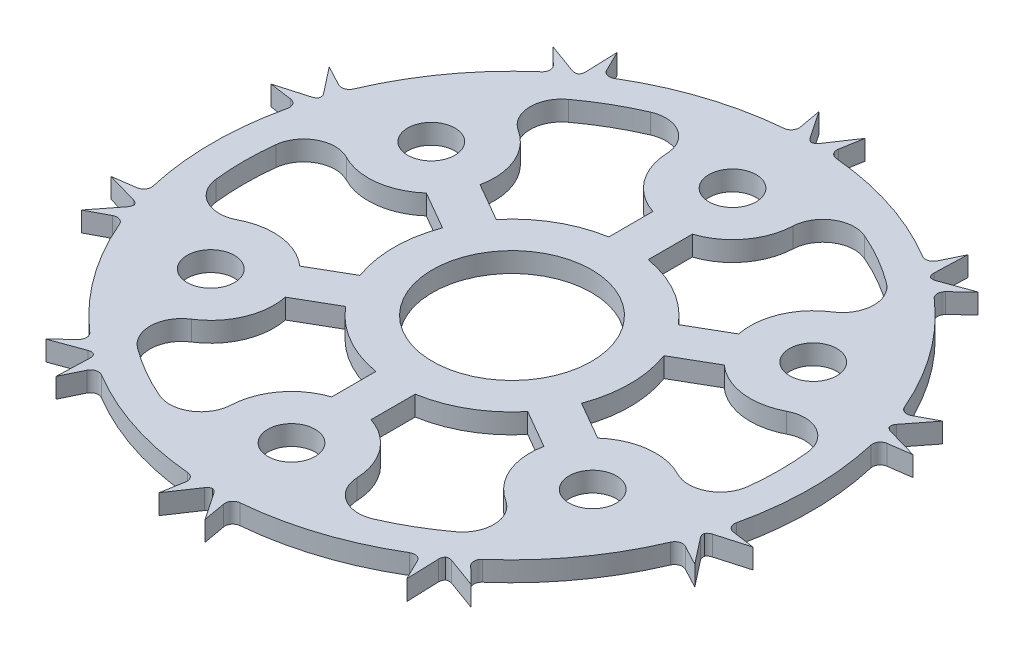
SolidWorks part; units mm, degrees
note: '?' marks a value the reader was unsure of.
material "Commercially Pure CP-Ti UNS R50700  Grade 4 (SS)"
ref_plane "Front Plane" through (0, 0, 0) normal (0, 0, 1) x (1, 0, 0)
ref_plane "Top Plane" through (0, 0, 0) normal (0, 1, 0) x (1, 0, 0)
ref_plane "Right Plane" through (0, 0, 0) normal (1, 0, 0) x (0, 0, -1)
other "Bounding Box"
ref_plane "Default Plane" through (13.8565, 3.175, 6.7999) normal (0, -1, 0) x (-1, 0, 0)
sketch "Sketch1" plane through (0, 0, 0) normal (0, 1, 0) x (1, 0, 0)
  line L0 (17.9605, -17.9605) -> (0, 0) construction
  line L1 (0, 0) -> (17.9605, 17.9605) construction
  line L2 (0, 0) -> (0, 25.4) construction
  circle A0 centre (0, 0) radius 25.4
  point P3 (0, 25.4)
  point P4 (25.4, 0)
  point P5 (-25.4, 0)
  point P6 (0, -25.4)
  point P7 (17.9605, 17.9605)
  point P8 (17.9605, -17.9605)
  dimension "D1" = 50.8
  dimension "D2" = 45
extrude "Boss-Extrude1" add sketch "Sketch1" along normal mid plane 15.24
ref_plane "Plane2" through (-25.4, 0, 0) normal (-1, 0, 0) x (0, 0, 1)
sketch "Sketch9" plane through (-25.4, 0, 0) normal (-1, 0, 0) x (0, 0, 1)
  line L0 (-0.635, -7.62) -> (0.635, -7.62)
  line L1 (-25.4, -7.62) -> (25.4, -7.62) construction
  line L2 (0.635, -7.62) -> (0.635, 0)
  line L3 (25.4, 7.62) -> (-25.4, 7.62) construction
  line L5 (-0.635, 0) -> (-0.635, -7.62)
  line L6 (0.635, -7.62) -> (0, -7.62) construction
  line L7 (0, -7.62) -> (0, 7.62) construction
  line L9 (-0.635, 0) -> (0.635, 0) construction
  line L10 (0.635, 0) -> (0.635, 7.62)
  line L11 (0.635, 7.62) -> (-0.635, 7.62)
  line L13 (-0.635, 7.62) -> (-0.635, 0)
  point P14 (0, 0)
  dimension "D2" = 1.27
extrude "Cut-Extrude4" cut sketch "Sketch9" against normal blind 0.635
sketch "Sketch4" plane through (0, 0, 0) normal (0, 0, 1) x (1, 0, 0)
  line L0 (-25.4, -7.62) -> (-22.225, -7.62)
  line L1 (-25.3921, -7.62) -> (25.4, -7.62) construction
  line L4 (25.4, 7.62) -> (-25.3921, 7.62) construction
  line L5 (-22.225, 7.62) -> (-25.4, 7.62)
  line L6 (-25.4, 7.62) -> (-25.4, -7.62)
  line L7 (-9.525, 0) -> (0, 0) construction
  line L8 (-22.225, -7.62) -> (-22.225, -5.08)
  line L9 (-22.225, -5.08) -> (-13.9469, -1.7687)
  line L10 (-13.9469, 1.7687) -> (-22.225, 5.08)
  line L11 (-22.225, 5.08) -> (-22.225, 7.62)
  arc A0 (-13.9469, 1.7687) -> (-13.9469, -1.7687) centre (-14.6544, 0) cw
  point P17 (-25.4, 0)
  dimension "D4" = 1.905
  dimension "D1" = 3.175
  dimension "D2" = 15.875
  dimension "D3" = 2.54
pattern_circular "CirPattern2" count 20 over 360 about axis through (0, 0, 0) along (0, 1, 0) of "Cut-Extrude4"
ref_axis "Axis1" through (0, -55, 0) along (0, 1, 0)
sketch "Sketch3" plane through (0, 7.62, 0) normal (0, 1, 0) x (1, 0, 0)
  line L0 (0, 0) -> (0, 17.78) construction
  line L1 (0, 17.78) -> (0, 25.4) construction
  circle A0 centre (0, 17.78) radius 1.397
  circle A1 centre (0, 0) radius 25.4 construction
  circle A2 centre (0, 17.78) radius 3.81
  dimension "D2" = 2.794
  dimension "D3" = 7.62
  dimension "D1" = 7.62
move or copy body "Body-Move/Copy1" [suppressed] parameters "D1"=0, "D2"=0, "D3"=0
revolve "Cut-Revolve2" cut sketch "Sketch4" angle 360 about axis through (0, -55, 0) along (0, 1, 0)
sketch "Sketch5" plane through (0, 7.62, 0) normal (0, 1, 0) x (1, 0, 0)
  circle A0 centre (0, 17.78) radius 3.81
  circle A1 centre (0, 17.78) radius 1.397 construction
  circle A3 centre (0, 17.78) radius 1.397
  circle A4 centre (0, 17.78) radius 3.81 construction
extrude "Boss-Extrude2" add sketch "Sketch5" against normal through all
sketch "Sketch12" plane through (0, 7.62, 0) normal (0, 1, 0) x (1, 0, 0)
  line L0 (-15.3979, 8.89) -> (0, 0) construction
  line L1 (-15.3979, -8.89) -> (-15.3979, 8.89) construction
  line L2 (-15.3979, 8.89) -> (0, 17.78) construction
  line L3 (-15.3979, -8.89) -> (0, 0) construction
  line L4 (0, 0) -> (0, 17.78) construction
  circle A0 centre (-15.3979, 8.89) radius 3.81
  circle A1 centre (0, 17.78) radius 3.81 construction
  dimension "D3" = 120
extrude "Boss-Extrude6" add sketch "Sketch12" against normal through all
sketch "Sketch17" plane through (0, 0, 0) normal (0, 1, 0) x (1, 0, 0)
  line L0 (0, 17.78) -> (0, 0) construction
  line L1 (0, 0) -> (-15.3979, 8.89) construction
  line L2 (0, 0) -> (-15.3979, -8.89) construction
  line L3 (-18.6975, -10.795) -> (-19.2474, -11.1125)
  line L4 (0, 21.59) -> (0, 22.225)
  line L5 (-17.3029, -5.5904) -> (-15.2513, -4.406)
  line L6 (-15.2513, 4.406) -> (-17.3029, 5.5904)
  line L7 (-13.4929, 12.1896) -> (-11.4413, 11.0051)
  line L8 (-3.81, 17.78) -> (-3.81, 15.411)
  circle A0 centre (0, 17.78) radius 3.81 construction
  circle A1 centre (-15.3979, 8.89) radius 3.81 construction
  arc A2 (0, 21.59) -> (-3.81, 17.78) centre (0, 17.78) ccw
  arc A3 (-13.4929, 12.1896) -> (-17.3029, 5.5904) centre (-15.3979, 8.89) ccw
  arc A5 (-3.81, 15.411) -> (-11.4413, 11.0051) centre (0, 0) ccw
  circle A6 centre (0, 17.78) radius 1.397 construction
  arc A7 (-17.3029, -5.5904) -> (-18.6975, -10.795) centre (-15.3979, -8.89) ccw
  circle A8 centre (0, 0) radius 22.225 construction
  circle A9 centre (0, 17.78) radius 1.397
  circle A10 centre (0, 0) radius 22.225 construction
  arc A11 (0, 22.225) -> (-19.2474, -11.1125) centre (0, 0) ccw
  arc A12 (-15.2513, 4.406) -> (-15.2513, -4.406) centre (0, 0) ccw
  circle A13 centre (-15.3979, 8.89) radius 1.397
  circle A15 centre (-15.3979, -8.89) radius 1.397
  dimension "D1" = 6.35
extrude "Cut-Extrude5" cut sketch "Sketch17" against normal through all both and the other way through all
pattern_circular "CirPattern1" count 3 over 360 about axis through (0, 0, 0) along (0, 1, 0) of "Boss-Extrude2", "Boss-Extrude6", "Cut-Extrude5"
sketch "Sketch24" plane through (0, -7.62, 0) normal (0, -1, 0) x (1, 0, 0)
  line L1 (5.4993, -9.525) -> (10.9985, 0)
  line L2 (10.9985, 0) -> (5.4993, 9.525)
  line L3 (5.4993, 9.525) -> (-5.4993, 9.525)
  line L4 (-5.4993, 9.525) -> (-10.9985, 0)
  line L5 (-10.9985, 0) -> (-5.4993, -9.525)
  line L6 (-5.4993, -9.525) -> (5.4993, -9.525)
  circle A0 centre (0, 0) radius 6.35 construction
  circle A1 centre (0, 0) radius 9.525 construction
  dimension "D1" = 12.7
  dimension "D2" = 19.05
extrude "Cut-Extrude7" cut sketch "Sketch24" against normal through all
sketch "Sketch33" [suppressed] plane through (0, -7.62, 0) normal (0, -1, 0) x (1, 0, 0)
  line L1 (-6.35, -6.35) -> (6.35, -6.35) construction
  line L2 (-6.35, -6.35) -> (-6.35, 6.35) construction
  line L3 (-6.35, 6.35) -> (6.35, 6.35) construction
  line L4 (6.35, -6.35) -> (6.35, 6.35) construction
  line L5 (-6.35, -6.35) -> (6.35, 6.35) construction
  line L6 (-6.35, 6.35) -> (6.35, -6.35) construction
  circle A0 centre (-6.35, 6.35) radius 2.4892
  circle A1 centre (6.35, 6.35) radius 2.4892
  circle A2 centre (6.35, -6.35) radius 2.4892
  circle A3 centre (-6.35, -6.35) radius 2.4892
  point P0 (0, 0)
  dimension "D1" = 4.9784
  dimension "D2" = 12.7
extrude "Cut-Extrude8" [suppressed] cut sketch "Sketch33" against normal through all
combine bodies "Combine3" [suppressed] bodies to combine 116 167
delete or keep bodies "Body-Delete/Keep 4" [suppressed] bodies 194
sketch "Sketch7" [suppressed] plane through (0, -8.255, 0) normal (0, -1, 0) x (1, 0, 0)
  circle A0 centre (0, 0) radius 44.45
  circle A1 centre (0, 0) radius 38.1 construction
  dimension "D1" = 6.35
extrude "Boss-Extrude4" [suppressed] add sketch "Sketch7" against normal offset from surface (19.685 mm away) 3.175 separate body
combine bodies "Combine2" [suppressed] operation type? add bodies to combine 110 114
sketch "Sketch15" [suppressed] plane through (0, 0, 0) normal (1, 0, 0) x (0, 0, -1)
  line L0 (-38.1, -8.255) -> (-43.18, -13.335)
  line L1 (-43.18, -13.335) -> (-36.83, -13.335)
  line L2 (-36.83, -13.335) -> (-31.75, -8.255)
  line L3 (-31.75, -8.255) -> (-38.1, -8.255)
  dimension "D1" = 5.08
  dimension "D2" = 45
  dimension "D3" = 6.35
ref_axis "Axis2" [suppressed] through (0, -9.0805, 0) along (0, 1, 0)?
revolve "Revolve1" [suppressed] add sketch "Sketch15" angle 360 about axis through (0, -9.0805, 0) along (0, 1, 0)
fillet "Fillet4" [suppressed] radius 6.35
sketch "Sketch27" [suppressed] plane through (0, 11.43, 0) normal (0, 1, 0) x (1, 0, 0)
  line L0 (37.5671, 6.35) -> (44.45, 6.35)
  line L1 (44.45, -6.35) -> (37.5671, -6.35)
  line L2 (38.1, 0) -> (44.45, 0) construction
  circle A0 centre (44.45, 0) radius 1.905
  arc A1 (37.5671, -6.35) -> (37.5671, 6.35) centre (0, 0) ccw
  circle A2 centre (0, 0) radius 38.1 construction
  arc A3 (44.45, 6.35) -> (44.45, -6.35) centre (44.45, 0) cw
  dimension "D2" = 3.81
  dimension "D3" = 6.35
  dimension "D1" = 6.35
extrude "Boss-Extrude13" [suppressed] add sketch "Sketch27" against normal blind 9.525
pattern_circular "CirPattern7" [suppressed] count 3 over 360
split "Split1" [suppressed] bodies to split 124
sketch "Sketch19" [suppressed] plane through (0, 11.43, 0) normal (0, 1, 0) x (1, 0, 0)
  line L0 (-20.447, 35.4152) -> (-19.177, 33.2155)
  line L1 (-20.447, -35.4152) -> (-19.177, -33.2155)
  line L2 (-40.894, 0) -> (0, 0) construction
  arc A0 (-19.177, 33.2155) -> (-19.177, -33.2155) centre (0, 0) ccw
  circle A1 centre (0, 0) radius 38.1 construction
  arc A2 (-20.447, 35.4152) -> (-20.447, -35.4152) centre (0, 0) ccw
  dimension "D2" = 2.54
  dimension "D3" = 0.254
  dimension "D1" = 120
extrude "Boss-Extrude10" [suppressed] add sketch "Sketch19" against normal blind 6.35 separate body
sketch "Sketch21" [suppressed] plane through (0, 11.43, 0) normal (0, 1, 0) x (1, 0, 0)
  line L0 (-19.177, 33.2155) -> (-19.05, 32.9956)
  line L1 (-19.177, -33.2155) -> (-19.05, -32.9956)
  line L2 (-19.177, 33.2155) -> (-20.447, 35.4152) construction
  line L3 (-20.447, -35.4152) -> (-19.177, -33.2155) construction
  arc A1 (-19.177, 33.2155) -> (-19.177, -33.2155) centre (0, 0) ccw construction
  arc A2 (-19.05, 32.9956) -> (-19.05, -32.9956) centre (0, 0) ccw
  arc A3 (-19.177, 33.2155) -> (-19.177, -33.2155) centre (0, 0) ccw
  circle A4 centre (0, 0) radius 38.1 construction
extrude "Boss-Extrude11" [suppressed] add sketch "Sketch21" against normal blind 3.1496
pattern_circular "CirPattern6" [suppressed] count 3 over 360
combine bodies "Combine4" [suppressed] bodies to combine 137 137 135 134
chamfer "Chamfer4" [suppressed] distance 0.635 angle 45
delete or keep bodies "Body-Delete/Keep 1" [suppressed] type delete bodies bodies 133
delete or keep bodies "Body-Delete/Keep 2" [suppressed] type delete bodies bodies 121
mirror "Mirror1" [suppressed] about plane through (0, 0, 0) normal (1, 0, 0)
delete or keep bodies "Body-Delete/Keep 3" [suppressed] type delete bodies bodies 121
sketch "Sketch28" [suppressed] plane through (0, 8.255, 0) normal (0, -1, 0) x (1, 0, 0)
  circle A0 centre (0, 0) radius 15.24
  dimension "D1" = 30.48
extrude "Boss-Extrude14" [suppressed] add sketch "Sketch28" along normal blind 0.635
sketch "Sketch29" [suppressed] plane through (0, 7.62, 0) normal (0, -1, 0) x (1, 0, 0)
  circle A0 centre (0, 0) radius 9.144
  dimension "D1" = 18.288
extrude "Boss-Extrude15" [suppressed] add sketch "Sketch29" along normal blind 10.16
sketch "Sketch30" plane through (0, -7.62, 0) normal (0, -1, 0) x (1, 0, 0)
  circle A12 centre (0, 0) radius 24.13
  circle A13 centre (0, 0) radius 21.59
  circle A14 centre (0, 0) radius 25.4 construction
  dimension "D1" = 1.27
  dimension "D2" = 2.54
extrude "Boss-Extrude16" add sketch "Sketch30" along normal blind 1.6002 separate body
sketch "Sketch31" plane through (0, -9.2202, 0) normal (0, -1, 0) x (1, 0, 0)
  line L0 (-5.08, 17.78) -> (-5.08, 23.5892)
  line L1 (-5.08, 23.5892) -> (5.08, 23.5892)
  line L2 (5.08, 23.5892) -> (5.08, 17.78)
  line L3 (0, 0) -> (0, 17.78) construction
  line L4 (-1.5875, 12.9544) -> (1.5875, 12.9544) construction
  line L5 (-1.5875, 12.9544) -> (-1.5875, 7.62)
  line L6 (-1.5875, 7.62) -> (1.5875, 7.62)
  line L7 (1.5875, 12.9544) -> (1.5875, 7.62)
  line L8 (-1.5875, 12.9544) -> (1.5875, 7.62) construction
  line L9 (-1.5875, 7.62) -> (1.5875, 12.9544) construction
  arc A0 (-1.5875, 12.9544) -> (-5.08, 17.78) centre (0, 17.78) cw
  circle A1 centre (0, 17.78) radius 1.905
  arc A2 (5.08, 17.78) -> (1.5875, 12.9544) centre (0, 17.78) cw
  circle A3 centre (0, 17.78) radius 1.397 construction
  circle A4 centre (0, 0) radius 24.13 construction
  point P0 (0, 10.2872)
  dimension "D1" = 3.175
  dimension "D2" = 3.81
  dimension "D3" = 7.62
  dimension "D4" = 3.175
extrude "Boss-Extrude17" add sketch "Sketch31" against normal up to surface (1.6002 mm away) up to face at (0, -7.62, -24.13)
fillet "Fillet6" radius 2.54 2 edges at (5.08, -8.4201, 20.9838) (-5.08, -8.4201, 20.9838)
pattern_circular "CirPattern8" count 6 over 360 about axis through (0, 0, 0) along (0, 1, 0) of "Boss-Extrude17", "Fillet6"
sketch "Sketch32" plane through (0, -9.2202, 0) normal (0, -1, 0) x (1, 0, 0)
  line L0 (0, 0) -> (-1.8604, 26.605) construction
  line L1 (1.8604, 26.605) -> (0.1905, 24.1292)
  line L2 (0, 0) -> (0, 26.67) construction
  line L3 (-1.4167, 24.0884) -> (-1.8604, 26.605)
  line L4 (-1.8604, 26.605) -> (-0.1905, 24.1292)
  line L5 (-0.1905, 24.1292) -> (-1.4167, 24.0884)
  line L6 (1.4167, 24.0884) -> (1.8604, 26.605)
  line L7 (0.1905, 24.1292) -> (1.4167, 24.0884)
  circle A0 centre (0, 0) radius 24.13 construction
  circle A1 centre (0, 0) radius 26.67 construction
  circle A2 centre (0, 0) radius 25.4 construction
  dimension "D2" = 1.27
  dimension "D1" = 6
  dimension "D3" = 30
  dimension "D4" = 4
extrude "Boss-Extrude18" add sketch "Sketch32" against normal up to surface (1.6002 mm away) up to face at (0, -7.62, -24.13)
fillet "Fillet7" radius 0.635 4 edges at (1.4167, -8.4201, 24.0884) (0.1905, -8.4201, 24.1292) (-0.1905, -8.4201, 24.1292) (-1.4167, -8.4201, 24.0884)
pattern_circular "CirPattern9" count 10 over 360 about axis through (0, 0, 0) along (0, 1, 0) of "Boss-Extrude18", "Fillet7"
sketch "Sketch34" plane through (0, -9.2202, 0) normal (0, -1, 0) x (1, 0, 0)
  circle A0 centre (0, 0) radius 6.4135
  circle A1 centre (0, 0) radius 9.525
  dimension "D1" = 12.827
  dimension "D2" = 19.05
extrude "Boss-Extrude19" add sketch "Sketch34" against normal up to surface (1.6002 mm away) up to face at (0, -7.62, 0)
delete or keep bodies "Body-Delete/Keep 5" bodies 197
